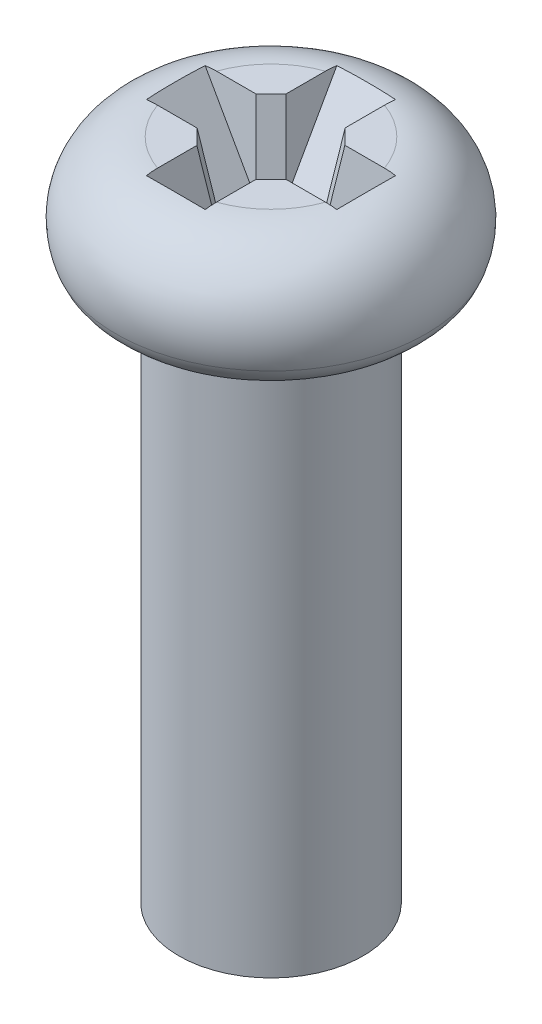
SolidWorks part; units mm, degrees
material "Plain Carbon Steel"
ref_plane "Front Plane" through (0, 0, 0) normal (0, 0, 1) x (1, 0, 0)
ref_plane "Top Plane" through (0, 0, 0) normal (0, 1, 0) x (1, 0, 0)
ref_plane "Right Plane" through (0, 0, 0) normal (1, 0, 0) x (0, 0, -1)
sketch "Sketch1" plane through (0, 0, 0) normal (0, 0, 1) x (1, 0, 0)
  line L0 (0, 9) -> (0, 0)
  line L1 (-1.25, 7.4) -> (-1.9, 7.4)
  line L4 (-1.25, 7.4) -> (-1.25, 0)
  line L5 (-1.25, 0) -> (0, 0)
  line L6 (0, 9) -> (-1.2072, 9)
  arc A2 (-1.9, 7.4) -> (-1.2072, 9) centre (-1.2072, 8.05) cw
  dimension "D1" = 2.5
  dimension "D5" = 1.9
  dimension "D2" = 9
  dimension "D3" = 3.8
  dimension "D4" = 7.4
revolve "Revolve1" add sketch "Sketch1" angle 360 about L0
fillet "Fillet1" radius 0.5 1 edges at (-1.9, 7.4, 0)
sketch "Sketch2" plane through (0, 9, 0) normal (0, 1, 0) x (1, 0, 0)
  line L1 (-0.4, -1.3) -> (0.4, -1.3)
  line L2 (-0.4, -1.3) -> (-0.4, 1.3)
  line L3 (-0.4, 1.3) -> (0.4, 1.3)
  line L4 (0.4, -1.3) -> (0.4, 1.3)
  line L5 (-0.4, -1.3) -> (0.4, 1.3) construction
  line L6 (-0.4, 1.3) -> (0.4, -1.3) construction
  point P0 (0, 0)
  dimension "D1" = 2.6
  dimension "D2" = 0.8
ref_plane "Plane1" through (0, 7.6, 0) normal (0, 1, 0) x (1, 0, 0)
sketch "Sketch3" plane through (0, 7.6, 0) normal (0, 1, 0) x (1, 0, 0)
  line L1 (0.2, 0.2) -> (-0.2, 0.2)
  line L2 (0.2, 0.2) -> (0.2, -0.2)
  line L3 (0.2, -0.2) -> (-0.2, -0.2)
  line L4 (-0.2, 0.2) -> (-0.2, -0.2)
  line L5 (0.2, 0.2) -> (-0.2, -0.2) construction
  line L6 (0.2, -0.2) -> (-0.2, 0.2) construction
  point P0 (0, 0)
  dimension "D1" = 0.4
loft "Cut-Loft1" cut profiles "Sketch2", "Sketch3"
pattern_circular "CirPattern1" count 2 over 90 about axis through (0, 0, 0) along (0, 1, 0) of "Cut-Loft1"
chamfer "Chamfer1" distance 0.2 angle 45 4 edges
